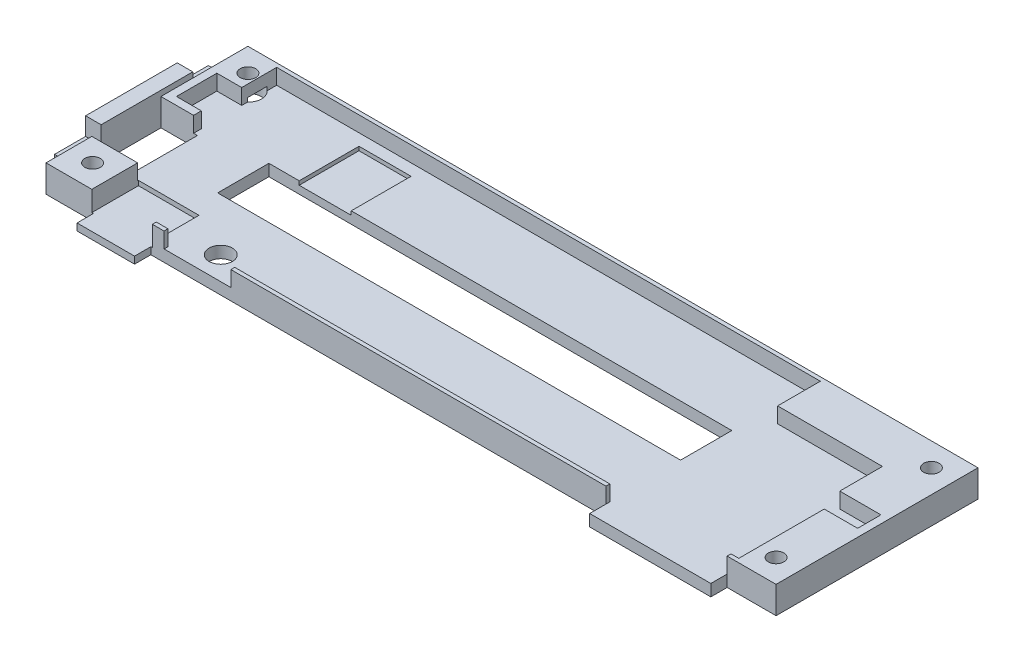
SolidWorks part; units mm, degrees
ref_plane "前视基准面" through (0, 0, 0) normal (0, 0, 1) x (1, 0, 0)
ref_plane "上视基准面" through (0, 0, 0) normal (0, 1, 0) x (1, 0, 0)
ref_plane "右视基准面" through (0, 0, 0) normal (1, 0, 0) x (0, 0, -1)
other "Configuration Table"
sketch "草图1" plane through (0, 0, 0) normal (0, 1, 0) x (1, 0, 0)
  line L1 (-47, -13) -> (47, -13)
  line L2 (-47, -13) -> (-47, 13)
  line L3 (-47, 13) -> (47, 13)
  line L4 (47, -13) -> (47, 13)
  line L5 (-47, -13) -> (47, 13) construction
  line L6 (-47, 13) -> (47, -13) construction
  circle A1 centre (-44, 10) radius 1
  circle A2 centre (-44, -10) radius 1
  circle A3 centre (44, 10) radius 1
  circle A4 centre (44, -10) radius 1
  point P0 (0, 0)
  dimension "D3" = 3
  dimension "D4" = 3
  dimension "D1" = 94
  dimension "D2" = 26
  dimension "D7" = 2
  dimension "D5" = 3
  dimension "D6" = 3
extrude "凸台-拉伸1" add sketch "草图1" along normal blind 3.5
sketch "草图2" plane through (0, 0, 0) normal (0, -1, 0) x (1, 0, 0)
  line L0 (-47, -13) -> (-47, 13) construction
  line L1 (-47, 7.1) -> (-42.3, 7.1)
  line L2 (-47, 7.1) -> (-47, -1.8)
  line L3 (-47, -1.8) -> (-42.3, -1.8)
  line L4 (-42.3, 7.1) -> (-42.3, -1.8)
  line L5 (-47, 13) -> (47, 13) construction
  line L6 (47, -13) -> (-47, -13) construction
  line L7 (-34.6, 0) -> (0, 0) construction
  line L8 (-34.6, 3.3) -> (25, 3.3)
  line L9 (-34.6, 3.3) -> (-34.6, -3.3)
  line L10 (-34.6, -3.3) -> (25, -3.3)
  line L11 (25, 3.3) -> (25, -3.3)
  line L12 (47, 13) -> (47, -13) construction
  dimension "D1" = 5.9
  dimension "D2" = 11.2
  dimension "D3" = 4.7
  dimension "D4" = 22
  dimension "D5" = 12.4
  dimension "D6" = 6.6
extrude "切除-拉伸1" cut sketch "草图2" against normal through all
sketch "草图3" plane through (0, 0, 0) normal (0, -1, 0) x (-1, 0, 0)
  line L0 (47, -13) -> (-47, -13) construction
  line L1 (31.8, -13) -> (23.2, -13)
  line L2 (31.8, -13) -> (31.8, -7)
  line L3 (31.8, -7) -> (23.2, -7)
  line L4 (23.2, -13) -> (23.2, -7)
  line L5 (47, -7.1) -> (47, -13) construction
  line L6 (-47, -13) -> (-47, 13) construction
  line L7 (31.8, -13) -> (23.2, -7) construction
  circle A0 centre (27.5, -10) radius 1.5
  dimension "D4" = 3
  dimension "D1" = 15.2
  dimension "D2" = 70.2
  dimension "D3" = 6
extrude "切除-拉伸2" cut sketch "草图3" against normal through all contours A0
sketch "草图4" plane through (0, 0, 0) normal (0, -1, 0) x (1, 0, 0)
  circle A0 centre (-44, 10) radius 1.75
  circle A1 centre (-44, -10) radius 1.75
  circle A2 centre (44, 10) radius 1.75
  circle A3 centre (44, -10) radius 1.75
  circle A4 centre (-44, 10) radius 1 construction
  circle A5 centre (-44, -10) radius 1 construction
  circle A6 centre (44, -10) radius 1 construction
  circle A7 centre (44, 10) radius 1 construction
  dimension "D1" = 3.5
extrude "切除-拉伸3" cut sketch "草图4" against normal offset from surface (2 mm away) 1.5 up to face at (-27.5, 3.5, 8.5)
sketch "草图5" plane through (0, 0, 13) normal (0, 0, 1) x (1, 0, 0)
  line L0 (-47, 3.5) -> (47, 3.5) construction
  line L1 (-41.1, 3.5) -> (-33.3, 3.5)
  line L2 (-41.1, 3.5) -> (-41.1, 0.9)
  line L3 (-41.1, 0.9) -> (-33.3, 0.9)
  line L4 (-33.3, 3.5) -> (-33.3, 0.9)
  line L5 (47, 3.5) -> (47, 0) construction
  line L6 (-31.8, 3.5) -> (-23.2, 3.5)
  line L7 (-31.8, 3.5) -> (-31.8, 1.5)
  line L8 (-31.8, 1.5) -> (-23.2, 1.5)
  line L9 (-23.2, 3.5) -> (-23.2, 1.5)
  line L10 (25.1, 3.5) -> (40.7, 3.5)
  line L11 (25.1, 3.5) -> (25.1, 1.5)
  line L12 (25.1, 1.5) -> (40.7, 1.5)
  line L13 (40.7, 3.5) -> (40.7, 1.5)
  line L14 (-47, 3.5) -> (-47, 0) construction
  dimension "D1" = 2
  dimension "D2" = 6.3
  dimension "D3" = 72.1
  dimension "D4" = 2.6
  dimension "D5" = 2
  dimension "D6" = 5.9
  dimension "D7" = 80.3
  dimension "D8" = 15.2
  dimension "D9" = 70.2
extrude "切除-拉伸4" cut sketch "草图5" against normal blind 6 contours L2 L3 L4 L1 | L8 L9 L6 L7
extrude "切除-拉伸5" cut sketch "草图5<3>" against normal blind 20 contours L13 L12 L11 L10
sketch "草图5<3>" plane through (0, 0, 13) normal (0, 0, 1) x (1, 0, 0) same geometry as "草图5"
sketch "草图6" plane through (0, 3.5, 0) normal (0, 1, 0) x (1, 0, 0)
  line L0 (47, 13) -> (-47, 13) construction
  line L1 (-42.8, 12.5) -> (27.2, 12.5)
  line L2 (-42.8, 12.5) -> (-42.8, -7.1)
  line L3 (-42.8, -7.1) -> (27.2, -7.1)
  line L4 (27.2, 12.5) -> (27.2, -7.1)
  line L5 (27.2, 1.5) -> (46, 1.5)
  line L6 (27.2, 1.5) -> (27.2, -1.5)
  line L7 (27.2, -1.5) -> (46, -1.5)
  line L8 (46, 1.5) -> (46, -1.5)
  line L9 (-23.2, -13) -> (25.1, -13) construction
  line L10 (41.7, -1.5) -> (-41.1, -1.5)
  line L11 (41.7, -1.5) -> (41.7, -12.5)
  line L12 (41.7, -12.5) -> (-41.1, -12.5)
  line L13 (-41.1, -1.5) -> (-41.1, -12.5)
  line L14 (0, 0) -> (46, 0) construction
  line L15 (-47, 13) -> (-47, 1.8) construction
  line L16 (-42.8, 8) -> (-46, 8)
  line L17 (-42.8, 8) -> (-42.8, 2.8)
  line L18 (-42.8, 2.8) -> (-46, 2.8)
  line L19 (-46, 8) -> (-46, 2.8)
  line L20 (-47, 1.8) -> (-42.3, 1.8) construction
  line L22 (-41.1, -7) -> (-41.1, -13) construction
  line L23 (-42.3, -7.1) -> (-47, -7.1) construction
  line L25 (47, -13) -> (47, 13) construction
  line L26 (40.7, 7) -> (40.7, -13) construction
  dimension "D1" = 0.5
  dimension "D2" = 0.5
  dimension "D3" = 3
  dimension "D4" = 1
  dimension "D5" = 5
  dimension "D6" = 4.2
  dimension "D7" = 1
  dimension "D8" = 1
  dimension "D9" = 1
  dimension "D10" = 70
extrude "切除-拉伸12" cut sketch "草图6" against normal blind 2 contours L16 L19 L18 L17 | L10 L13 L12 L11 | L5 L8 L7 L6 | L1 L4 L3 L2
sketch "草图7" plane through (0, 1.5, 0) normal (0, 1, 0) x (1, 0, 0)
  line L0 (25, 3.3) -> (-34.6, 3.3) construction
  line L1 (-30.7, 3.3) -> (-24, 3.3)
  line L2 (-30.7, 3.3) -> (-30.7, 11)
  line L3 (-30.7, 11) -> (-24, 11)
  line L4 (-24, 3.3) -> (-24, 11)
  line L5 (-47, 13) -> (-47, 1.8) construction
  line L6 (47, -13) -> (47, 13) construction
  line L7 (47, 13) -> (-47, 13) construction
  dimension "D1" = 16.3
  dimension "D2" = 71
  dimension "D3" = 2
extrude "切除-拉伸13" cut sketch "草图7" against normal blind 0.5
sketch "草图8" plane through (0, 0, 13) normal (0, 0, 1) x (1, 0, 0)
  line L0 (-41.1, 0.9) -> (-33.3, 0.9) construction
  line L1 (-40.9, 0.9) -> (-33.5, 0.9)
  line L2 (-40.9, 0.9) -> (-40.9, 0)
  line L3 (-40.9, 0) -> (-33.5, 0)
  line L4 (-33.5, 0.9) -> (-33.5, 0)
  line L5 (-47, 0) -> (47, 0) construction
  line L7 (-41.1, 3.5) -> (-41.1, 0.9) construction
  line L8 (-33.3, 3.5) -> (-33.3, 0.9) construction
  line L9 (47, 3.5) -> (47, 0) construction
  line L13 (25.1, 0) -> (40.7, 0)
  line L14 (25.1, 0) -> (25.1, 1.5)
  line L15 (25.1, 1.5) -> (40.7, 1.5)
  line L16 (40.7, 0) -> (40.7, 1.5)
  point P22 (22.9952, 1.5)
  dimension "D1" = 0.2
  dimension "D2" = 0.2
  dimension "D3" = 15.6
  dimension "D4" = 6.3
  dimension "D5" = 1.5
extrude "凸台-拉伸2" add sketch "草图8" along normal blind 2.1
sketch "草图10" plane through (-47, 0, 0) normal (-1, 0, 0) x (0, 0, 1)
  line L0 (-13, 0) -> (-1.8, 0) construction
  line L1 (-9.9, 0) -> (9.9, 0)
  line L2 (-9.9, 0) -> (-9.9, 1.9)
  line L3 (-9.9, 1.9) -> (9.9, 1.9)
  line L4 (9.9, 0) -> (9.9, 1.9)
  line L10 (-5.9, 4.2) -> (5.9, 4.2)
  line L11 (-5.9, 4.2) -> (-5.9, 0)
  line L12 (-5.9, 0) -> (5.9, 0)
  line L13 (5.9, 4.2) -> (5.9, 0)
  dimension "D1" = 19.8
  dimension "D2" = 1.9
  dimension "D3" = 11.8
  dimension "D4" = 4.2
extrude "凸台-拉伸3" add sketch "草图10" along normal blind 2 contours L2 L3 L4 L1 | L11 L12 L13 L10
